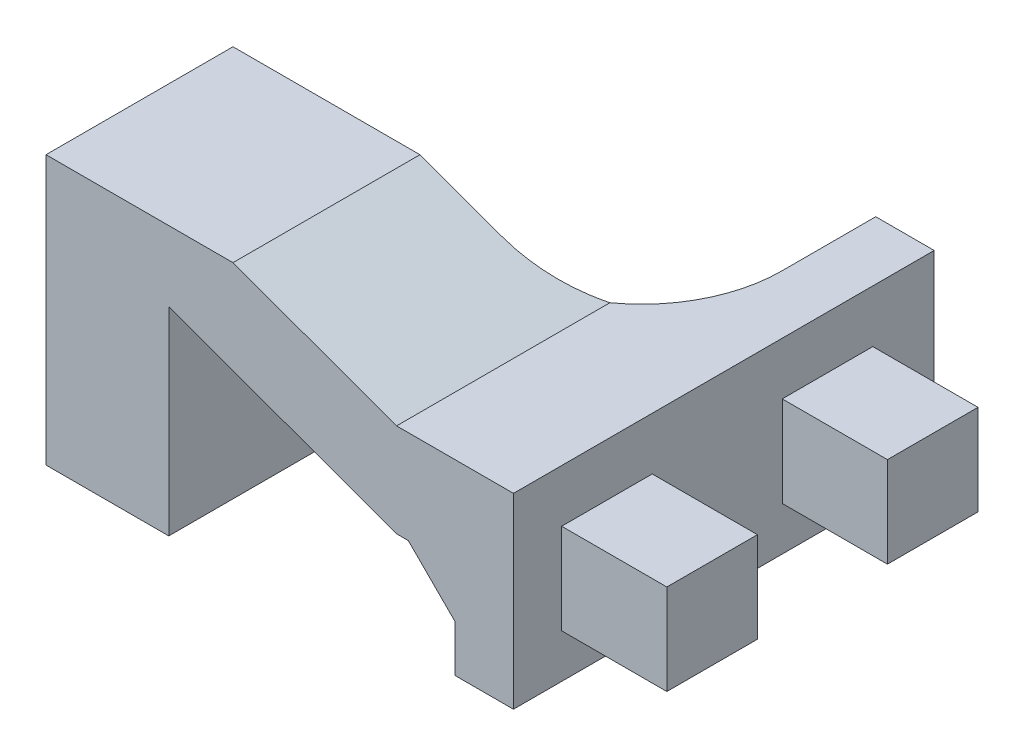
SolidWorks part; units mm, degrees
ref_plane "Front Plane" through (0, 0, 0) normal (0, 0, 1) x (1, 0, 0)
ref_plane "Top Plane" through (0, 0, 0) normal (0, 1, 0) x (1, 0, 0)
ref_plane "Right Plane" through (0, 0, 0) normal (1, 0, 0) x (0, 0, -1)
sketch "Sketch1" plane through (0, 0, 0) normal (0, 0, 1) x (1, 0, 0)
  line L0 (0, 3.5) -> (0, 11.5)
  line L1 (0, 11.5) -> (-5, 11.5)
  line L2 (-5, 11.5) -> (-5, 7.5)
  line L3 (-5, 7.5) -> (-4.5, 7.5)
  line L4 (-2.5, 5.5) -> (-2.5, 3.5)
  line L5 (-2.5, 3.5) -> (0, 3.5)
  line L6 (-4.5, 7.5) -> (-2.5, 5.5)
  line L7 (0, 9.25) -> (4.5, 9.25)
  line L8 (4.5, 9.25) -> (4.5, 5.375)
  line L9 (4.5, 5.375) -> (0, 5.375)
  line L10 (-2.5, 5.5) -> (-2.5, 11.5)
  line L11 (-20, 11.0478) -> (-20, 2.5478)
  line L12 (-20, 2.5478) -> (-14.7475, 2.5478)
  line L13 (-5, 11.5) -> (-12, 14.0478)
  line L14 (-12, 14.0478) -> (-20, 14.0478)
  line L15 (-20, 14.0478) -> (-20, 11.0478)
  line L16 (-20, 11.0478) -> (-14.7475, 11.0478)
  line L17 (-14.7475, 11.0478) -> (-5, 7.5)
  line L18 (-14.7475, 2.5478) -> (-14.7475, 11.0478)
  point P6 (-2.5, 7.5)
  point P15 (4.5, 7.3125)
  dimension "D1" = 8
  dimension "D2" = 5
  dimension "D3" = 2.5
  dimension "D4" = 4.5
  dimension "D5" = 3.875
  dimension "D6" = 3.5
  dimension "D8" = 2.25
  dimension "D9" = 3
  dimension "D10" = 4
  dimension "D11" = 8.5
  dimension "D12" = 8
  dimension "D13" = 15
  dimension "D14" = 160
extrude "Boss-Extrude1" add sketch "Sketch1" against normal mid plane 8 contours L3 L6 L4 L5 L0 L1 L2 | L16 L17 L2 L13 L14 L15 | L12 L18 L16 L11 | L5 L0 L1 L2 L3 L6 L4 region at (-1.25, 7.5, 0) region at (-11.9861, 11.57, 0) region at (-17.3737, 6.7978, 0)
extrude "Boss-Extrude4" add sketch "Sketch1<7>" against normal blind 14 contours L10 L4 L5 L0 L1 region at (-1.25, 7.5, 0)
sketch "Sketch1<7>" plane through (0, 0, 0) normal (0, 0, 1) x (1, 0, 0) same geometry as "Sketch1"
extrude "Boss-Extrude2" add sketch "Sketch1<3>" along normal mid plane 3.875 contours L9 L8 L7 L0 region at (2.25, 7.3125, 0)
sketch "Sketch1<3>" plane through (0, 0, 0) normal (0, 0, 1) x (1, 0, 0) same geometry as "Sketch1"
extrude "Boss-Extrude5" add sketch "Sketch1<8>" along normal blind 3.875 from offset 11.375 contours L9 L8 L7 L0 region at (2.25, 7.3125, 0) offset against normal yes
sketch "Sketch1<8>" plane through (0, 0, 0) normal (0, 0, 1) x (1, 0, 0) same geometry as "Sketch1"
fillet "Fillet1" radius 6 1 edges at (-2.5, 8.5, -4)
